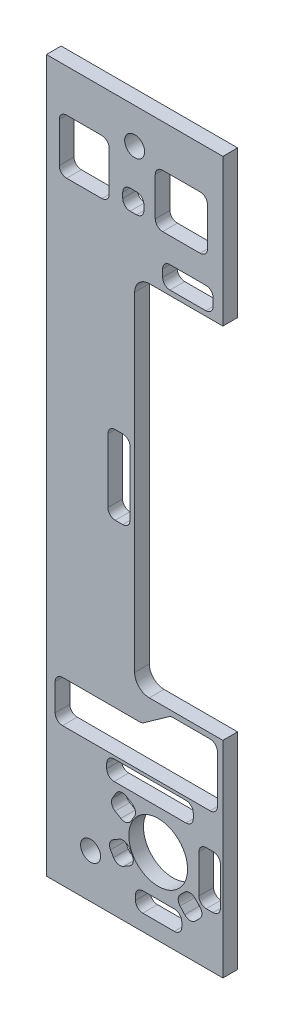
SolidWorks part; units mm, degrees
ref_plane "Front Plane" through (0, 0, 0) normal (0, 0, 1) x (1, 0, 0)
ref_plane "Top Plane" through (0, 0, 0) normal (0, 1, 0) x (1, 0, 0)
ref_plane "Right Plane" through (0, 0, 0) normal (1, 0, 0) x (0, 0, -1)
sketch "Sketch1" plane through (0, 0, 0) normal (0, 0, 1) x (1, 0, 0)
  line L8 (0, 0) -> (0, 44.45)
  line L9 (0, 44.45) -> (-15.875, 44.45)
  line L10 (-19.05, 47.625) -> (-19.05, 118.745)
  line L11 (-15.875, 121.92) -> (0, 121.92)
  line L12 (0, 121.92) -> (0, 153.67)
  line L13 (0, 153.67) -> (-38.1, 153.67)
  line L14 (-38.1, 153.67) -> (-38.1, 0)
  line L15 (-38.1, 0) -> (0, 0)
  line L16 (0, 0) -> (0, 44.45)
  line L17 (0, 44.45) -> (-15.875, 44.45)
  line L18 (-19.05, 47.625) -> (-19.05, 118.745)
  line L19 (-15.875, 121.92) -> (0, 121.92)
  line L20 (0, 121.92) -> (0, 153.67)
  line L21 (0, 153.67) -> (-38.1, 153.67)
  line L22 (-38.1, 153.67) -> (-38.1, 0)
  line L23 (-38.1, 0) -> (0, 0)
  arc A2 (-19.05, 47.625) -> (-15.875, 44.45) centre (-15.875, 47.625) ccw
  arc A3 (-15.875, 121.92) -> (-19.05, 118.745) centre (-15.875, 118.745) ccw
  arc A4 (-19.05, 47.625) -> (-15.875, 44.45) centre (-15.875, 47.625) ccw
  arc A5 (-15.875, 121.92) -> (-19.05, 118.745) centre (-15.875, 118.745) ccw
  dimension "D1" = 0
extrude "Boss-Extrude1" add sketch "Sketch1" along normal blind 3.175
hole_wizard "#6 Clearance Hole1" positions "Sketch3" profile "Sketch2" hole size "#6" standard "ANSI Inch" end condition through all
sketch "Sketch3" plane through (0, 0, 0) normal (0, 0, -1) x (-1, 0, 0)
  point P0 (28.575, 9.525)
  point P3 (19.05, 146.05)
sketch "Sketch2" plane through (-28.575, 9.525, 0) normal (1, 0, 0) x (0, 1, 0)
  line L0 (0, 0) -> (0, 3.175)
  line L1 (0, 3.175) -> (2.1526, 3.175)
  line L2 (2.1526, 3.175) -> (2.1526, 0)
  line L5 (2.1526, 0) -> (0, 0)
  line L11 (0, -6.35) -> (0, 107.95) construction
  dimension "Thru Hole Dia." = 4.3053
  dimension "Thru Hole Depth" = 3.175
hole_wizard "1/2 (0.5) Diameter Hole1" positions "Sketch5" profile "Sketch4" hole size "1/2" standard "ANSI Inch" end condition through all
sketch "Sketch5" plane through (0, 0, 0) normal (0, 0, -1) x (-1, 0, 0)
  point P0 (13.97, 16.51)
sketch "Sketch4" plane through (-13.97, 16.51, 0) normal (1, 0, 0) x (0, 1, 0)
  line L0 (0, 0) -> (0, 3.175)
  line L1 (0, 3.175) -> (6.35, 3.175)
  line L2 (6.35, 3.175) -> (6.35, 0)
  line L5 (6.35, 0) -> (0, 0)
  line L11 (0, -6.35) -> (0, 107.95) construction
  dimension "Thru Hole Dia." = 12.7
  dimension "Thru Hole Depth" = 3.175
sketch "Sketch6" plane through (0, 0, 0) normal (0, 0, -1) x (-1, 0, 0)
  line L0 (2.0861, 126.1244) -> (2.0861, 124.5436)
  line L1 (3.6736, 127.7119) -> (11.4156, 127.7119)
  line L2 (13.0031, 126.1244) -> (13.0031, 124.5436)
  line L3 (11.4156, 122.9561) -> (3.6736, 122.9561)
  line L4 (20.0337, 89.3692) -> (20.0337, 75.5814)
  line L5 (21.6212, 73.9939) -> (23.2419, 73.9939)
  line L6 (24.8294, 75.5814) -> (24.8294, 89.3692)
  line L7 (23.2419, 90.9567) -> (21.6212, 90.9567)
  line L8 (2.7596, 43.3215) -> (10.7671, 43.3215)
  line L9 (11.6877, 43.0272) -> (17.0516, 39.2089)
  line L10 (17.9723, 38.9146) -> (34.6277, 38.9146)
  line L11 (36.2152, 37.3271) -> (36.2152, 31.4793)
  line L12 (34.6277, 29.8918) -> (2.7596, 29.8918)
  line L13 (1.1721, 31.4793) -> (1.1721, 41.734)
  line L14 (23.4963, 29.2352) -> (7.9812, 29.2352)
  line L15 (6.3937, 27.6477) -> (6.3937, 26.5976)
  line L16 (7.9812, 25.0101) -> (23.4963, 25.0101)
  line L17 (25.0838, 26.5976) -> (25.0838, 27.6477)
  line L18 (2.1139, 22.5862) -> (3.5924, 22.5862)
  line L19 (5.1799, 20.9987) -> (5.1799, 12.7556)
  line L20 (3.5924, 11.1681) -> (2.1139, 11.1681)
  line L21 (0.5264, 12.7556) -> (0.5264, 20.9987)
  line L22 (18.8798, 6.0818) -> (18.8798, 5.0739)
  line L23 (17.2923, 3.4864) -> (10.4639, 3.4864)
  line L24 (8.8764, 5.0739) -> (8.8764, 6.0818)
  line L25 (10.4639, 7.6693) -> (17.2923, 7.6693)
  line L26 (6.031, 11.9253) -> (4.9832, 10.8775)
  line L27 (4.9832, 8.6324) -> (5.9433, 7.6723)
  line L28 (8.2494, 7.7368) -> (9.2385, 8.8433)
  line L29 (9.1775, 11.0239) -> (8.2761, 11.9253)
  line L30 (20.2037, 14.2118) -> (19.5506, 13.0904)
  line L31 (20.1234, 10.9196) -> (21.4392, 10.1533)
  line L32 (23.6099, 10.7261) -> (24.2631, 11.8475)
  line L33 (23.6903, 14.0183) -> (22.3745, 14.7846)
  line L34 (19.098, 20.675) -> (19.8549, 19.3952)
  line L35 (22.0294, 18.8367) -> (23.2732, 19.5723)
  line L36 (23.8316, 21.7468) -> (23.0747, 23.0266)
  line L37 (20.9002, 23.585) -> (19.6564, 22.8495)
  line L39 (4.9073, 144.5654) -> (13.0155, 144.5654)
  line L40 (3.3198, 142.9779) -> (3.3198, 134.6796)
  line L41 (4.9073, 133.0921) -> (13.0155, 133.0921)
  line L42 (14.603, 142.9779) -> (14.603, 134.6796)
  line L43 (18.6391, 137.7194) -> (20.0337, 137.7194)
  line L44 (17.0516, 136.1319) -> (17.0516, 134.9965)
  line L45 (18.6391, 133.409) -> (20.0337, 133.409)
  line L46 (21.6212, 136.1319) -> (21.6212, 134.9965)
  line L47 (26.1425, 144.502) -> (33.7435, 144.502)
  line L48 (24.555, 142.9145) -> (24.555, 134.2992)
  line L49 (26.1425, 132.7117) -> (33.7435, 132.7117)
  line L50 (35.331, 142.9145) -> (35.331, 134.2992)
  arc A0 (23.2732, 19.5723) -> (23.8316, 21.7468) centre (22.4651, 20.9387) ccw
  arc A1 (19.098, 20.675) -> (19.6564, 22.8495) centre (20.4645, 21.4831) cw
  arc A2 (21.4392, 10.1533) -> (23.6099, 10.7261) centre (22.2381, 11.5251) ccw
  arc A3 (20.2037, 14.2118) -> (22.3745, 14.7846) centre (21.5755, 13.4129) cw
  arc A4 (5.9433, 7.6723) -> (8.2494, 7.7368) centre (7.0659, 8.7948) ccw
  arc A5 (6.031, 11.9253) -> (8.2761, 11.9253) centre (7.1535, 10.8028) cw
  arc A6 (8.8764, 6.0818) -> (10.4639, 7.6693) centre (10.4639, 6.0818) cw
  arc A7 (18.8798, 6.0818) -> (17.2923, 7.6693) centre (17.2923, 6.0818) ccw
  arc A8 (5.1799, 12.7556) -> (3.5924, 11.1681) centre (3.5924, 12.7556) cw
  arc A9 (2.1139, 22.5862) -> (0.5264, 20.9987) centre (2.1139, 20.9987) ccw
  arc A10 (7.9812, 29.2352) -> (6.3937, 27.6477) centre (7.9812, 27.6477) ccw
  arc A11 (23.4963, 29.2352) -> (25.0838, 27.6477) centre (23.4963, 27.6477) cw
  arc A12 (2.7596, 29.8918) -> (1.1721, 31.4793) centre (2.7596, 31.4793) cw
  arc A13 (34.6277, 38.9146) -> (36.2152, 37.3271) centre (34.6277, 37.3271) cw
  arc A14 (36.2152, 31.4793) -> (34.6277, 29.8918) centre (34.6277, 31.4793) cw
  arc A15 (17.0516, 39.2089) -> (17.9723, 38.9146) centre (17.9723, 40.5021) ccw
  arc A16 (10.7671, 43.3215) -> (11.6877, 43.0272) centre (10.7671, 41.734) cw
  arc A17 (2.7596, 43.3215) -> (1.1721, 41.734) centre (2.7596, 41.734) ccw
  arc A18 (20.0337, 75.5814) -> (21.6212, 73.9939) centre (21.6212, 75.5814) ccw
  arc A19 (13.0031, 124.5436) -> (11.4156, 122.9561) centre (11.4156, 124.5436) cw
  arc A20 (20.0337, 89.3692) -> (21.6212, 90.9567) centre (21.6212, 89.3692) cw
  arc A21 (2.0861, 126.1244) -> (3.6736, 127.7119) centre (3.6736, 126.1244) cw
  arc A22 (2.0861, 124.5436) -> (3.6736, 122.9561) centre (3.6736, 124.5436) ccw
  arc A23 (11.4156, 127.7119) -> (13.0031, 126.1244) centre (11.4156, 126.1244) cw
  arc A24 (23.2419, 73.9939) -> (24.8294, 75.5814) centre (23.2419, 75.5814) ccw
  arc A25 (24.8294, 89.3692) -> (23.2419, 90.9567) centre (23.2419, 89.3692) ccw
  arc A26 (19.5506, 13.0904) -> (20.1234, 10.9196) centre (20.9224, 12.2914) ccw
  arc A27 (24.2631, 11.8475) -> (23.6903, 14.0183) centre (22.8913, 12.6465) ccw
  arc A28 (10.4639, 3.4864) -> (8.8764, 5.0739) centre (10.4639, 5.0739) cw
  arc A29 (18.8798, 5.0739) -> (17.2923, 3.4864) centre (17.2923, 5.0739) cw
  arc A30 (23.4963, 25.0101) -> (25.0838, 26.5976) centre (23.4963, 26.5976) ccw
  arc A31 (6.3937, 26.5976) -> (7.9812, 25.0101) centre (7.9812, 26.5976) ccw
  arc A32 (3.5924, 22.5862) -> (5.1799, 20.9987) centre (3.5924, 20.9987) cw
  arc A33 (2.1139, 11.1681) -> (0.5264, 12.7556) centre (2.1139, 12.7556) cw
  arc A34 (4.9832, 10.8775) -> (4.9832, 8.6324) centre (6.1057, 9.755) ccw
  arc A35 (9.2385, 8.8433) -> (9.1775, 11.0239) centre (8.055, 9.9013) ccw
  arc A36 (19.8549, 19.3952) -> (22.0294, 18.8367) centre (21.2213, 20.2032) ccw
  arc A37 (23.0747, 23.0266) -> (20.9002, 23.585) centre (21.7083, 22.2186) ccw
  arc A38 (33.7435, 144.502) -> (35.331, 142.9145) centre (33.7435, 142.9145) cw
  arc A39 (24.555, 134.2992) -> (26.1425, 132.7117) centre (26.1425, 134.2992) ccw
  arc A40 (33.7435, 132.7117) -> (35.331, 134.2992) centre (33.7435, 134.2992) ccw
  arc A41 (26.1425, 144.502) -> (24.555, 142.9145) centre (26.1425, 142.9145) ccw
  arc A42 (20.0337, 137.7194) -> (21.6212, 136.1319) centre (20.0337, 136.1319) cw
  arc A43 (17.0516, 134.9965) -> (18.6391, 133.409) centre (18.6391, 134.9965) ccw
  arc A44 (20.0337, 133.409) -> (21.6212, 134.9965) centre (20.0337, 134.9965) ccw
  arc A45 (18.6391, 137.7194) -> (17.0516, 136.1319) centre (18.6391, 136.1319) ccw
  arc A46 (13.0155, 144.5654) -> (14.603, 142.9779) centre (13.0155, 142.9779) cw
  arc A47 (3.3198, 134.6796) -> (4.9073, 133.0921) centre (4.9073, 134.6796) ccw
  arc A48 (13.0155, 133.0921) -> (14.603, 134.6796) centre (13.0155, 134.6796) ccw
  arc A49 (4.9073, 144.5654) -> (3.3198, 142.9779) centre (4.9073, 142.9779) ccw
  dimension "D1" = 1.5875
  dimension "D2" = 1.5875
  dimension "D3" = 1.5875
  dimension "D4" = 1.5875
extrude "Cut-Extrude1" cut sketch "Sketch6" against normal through all
